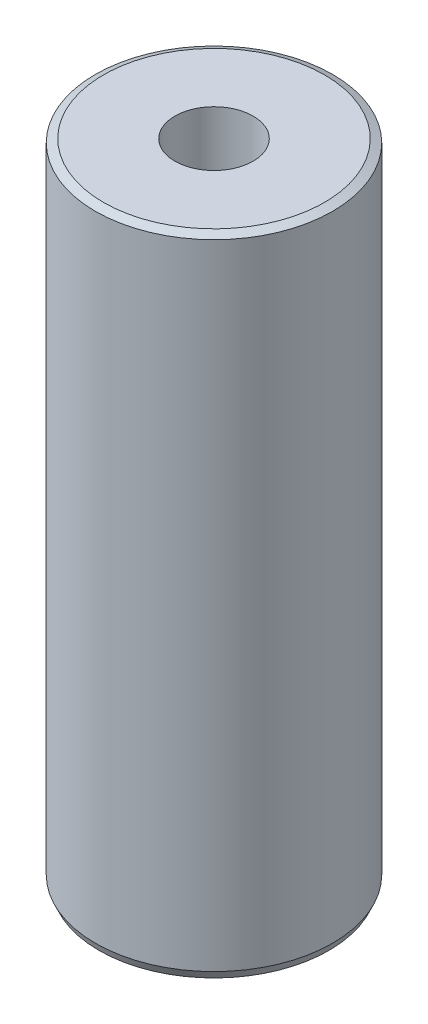
SolidWorks part; units mm, degrees
ref_plane "Front Plane" through (0, 0, 0) normal (0, 0, 1) x (1, 0, 0)
ref_plane "Top Plane" through (0, 0, 0) normal (0, 1, 0) x (1, 0, 0)
ref_plane "Right Plane" through (0, 0, 0) normal (1, 0, 0) x (0, 0, -1)
sketch "Sketch1" plane through (0, 0, 0) normal (0, 1, 0) x (1, 0, 0)
  circle A0 centre (0, 0) radius 60
  dimension "SHAFT_OD" = 120
extrude "Boss-Extrude1" add sketch "Sketch1" along normal blind 326.5592
sketch "Sketch2" plane through (0, 0, 0) normal (0, 1, 0) x (1, 0, 0)
  circle A0 centre (0, 0) radius 19.7879
  dimension "BORE_D" = 39.5758
extrude "Cut-Extrude1" cut sketch "Sketch2" along normal through all
chamfer "Chamfer1" distance 1.8501 angle 65.75 2 edges at (0, 326.5592, 60) (0, 0, 60) first distance on face at (0, 326.5592, 60) first distance on face at (0, 0, 19.7879)
